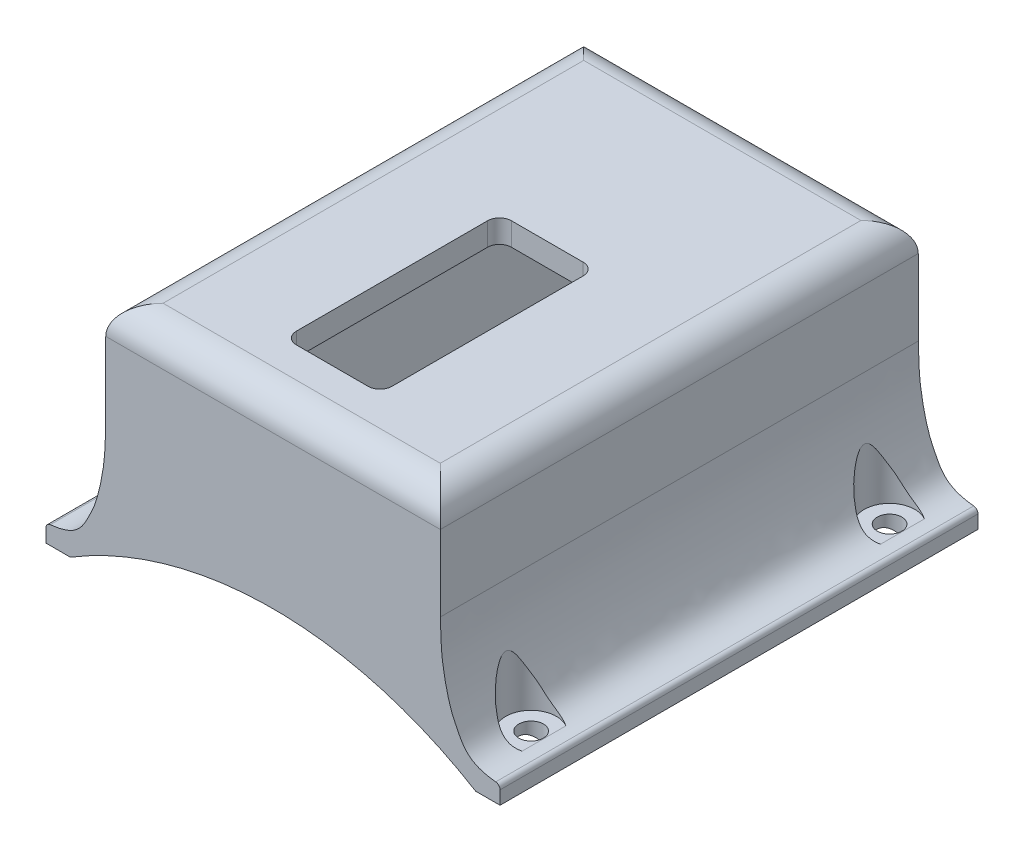
SolidWorks part; units mm, degrees
ref_plane "Front Plane" through (0, 0, 0) normal (0, 0, 1) x (1, 0, 0)
ref_plane "Top Plane" through (0, 0, 0) normal (0, 1, 0) x (1, 0, 0)
ref_plane "Right Plane" through (0, 0, 0) normal (1, 0, 0) x (0, 0, -1)
ref_axis "Axis1" through (0, 0, -60.9441) along (0, 0, 1)
sketch "Sketch1" plane through (0, 0, 0) normal (0, 1, 0) x (1, 0, 0)
  line L7 (22.225, -31.75) -> (-22.225, -31.75)
  line L8 (22.225, -31.75) -> (22.225, 31.75)
  line L9 (22.225, 31.75) -> (-22.225, 31.75)
  line L10 (-22.225, -31.75) -> (-22.225, 31.75)
  line L11 (22.225, -31.75) -> (-22.225, 31.75) construction
  line L12 (22.225, 31.75) -> (-22.225, -31.75) construction
  point P0 (0, 0)
  point P6 (0, 0)
  dimension "D1" = 44.45
  dimension "D3" = 63.5
extrude "Boss-Extrude1" add sketch "Sketch1" along normal blind 27.7622
sketch "Sketch3" plane through (0, 0, 0) normal (0, -1, 0) x (1, 0, 0)
  line L1 (19.304, -28.575) -> (-19.304, -28.575)
  line L2 (19.304, -28.575) -> (19.304, 27.94)
  line L3 (19.304, 27.94) -> (-19.304, 27.94)
  line L4 (-19.304, -28.575) -> (-19.304, 27.94)
  line L5 (19.304, -28.575) -> (-19.304, 27.94) construction
  line L6 (19.304, 27.94) -> (-19.304, -28.575) construction
  line L7 (22.225, -31.75) -> (-22.225, -31.75) construction
  point P0 (0, -0.3175)
  dimension "D1" = 38.608
  dimension "D2" = 56.515
  dimension "D3" = 3.175
extrude "Cut-Extrude2" cut sketch "Sketch3" against normal blind 24.7142
sketch "Sketch2" plane through (0, 0, -31.75) normal (0, 0, -1) x (-1, 0, 0)
  line L0 (-19.304, 0) -> (19.304, 0) construction
  line L3 (-14.2875, 1.7214) -> (-14.2875, 15.7951)
  line L5 (5.3975, 24.6851) -> (-5.3975, 24.6851)
  line L8 (-22.225, 0) -> (22.225, 0) construction
  line L11 (14.2875, 15.7951) -> (14.2875, 1.7214)
  arc A1 (5.3975, 24.6851) -> (10.4775, 19.6051) centre (5.3975, 19.6051) cw
  arc A2 (-5.3975, 24.6851) -> (-10.4775, 19.6051) centre (-5.3975, 19.6051) ccw
  arc A4 (14.2875, 1.7214) -> (-14.2875, 1.7214) centre (0, -48.0859) ccw
  circle A5 centre (0, -48.0859) radius 51.816 construction
  arc A6 (14.2875, 15.7951) -> (10.4775, 19.6051) centre (10.4775, 15.7951) ccw
  arc A7 (-10.4775, 19.6051) -> (-14.2875, 15.7951) centre (-10.4775, 15.7951) ccw
  point P3 (0, 3.7301)
  point P12 (0, 0)
  point P18 (-10.4775, 24.6851)
  point P19 (0, 0)
  point P23 (0, 0)
  point P24 (0, 0)
  point P25 (0, 0)
  point P27 (0, 0)
  point P28 (14.2875, 19.6051)
  point P31 (0, 0)
  point P32 (0, 0)
  point P33 (0, 0)
  point P34 (0, 0)
  point P35 (0, 0)
  point P36 (-14.2875, 13.7552)
  point P37 (0, 0)
  point P38 (0, 0)
  point P39 (0, 24.6851)
  dimension "D1" = 103.632
  dimension "D3" = 38.608
  dimension "D2" = 20.955
  dimension "D5" = 28.575
  dimension "D7" = 15.875
extrude "Cut-Extrude3" cut sketch "Sketch2" against normal up to surface (3.175 mm away) up to face at (0, 12.3571, -28.575)
sketch "Sketch6" plane through (0, 0, -31.75) normal (0, 0, -1) x (-1, 0, 0)
  line L1 (-22.225, 27.7622) -> (-22.225, 0) construction
  line L3 (-22.225, 0) -> (-22.225, 13.8811)
  line L6 (0, 15.2692) -> (0, -15.2692) construction
  line L9 (22.225, 0) -> (22.225, 13.8811)
  line L10 (-30.1625, -3.81) -> (30.1625, -3.81)
  line L11 (30.1625, -3.81) -> (30.1625, -1.4483)
  line L12 (-22.225, 0) -> (22.225, 0)
  line L13 (-30.1625, -1.4483) -> (-30.1625, -3.81)
  spline S0 degree 3 poles (-22.225, 13.8811) (-22.3095, 11.7348) (-22.2934, 9.3495) (-23.3442, 4.4268) (-25.2313, 0.5556) (-26.0119, -1.1813) (-30.1625, -1.4483) knots 0 0 0 0 0.208478 0.455524 0.521663 1 1 1 1
  spline S1 degree 3 poles (22.225, 13.8811) (22.3095, 11.7348) (22.2934, 9.3495) (23.3442, 4.4268) (25.2313, 0.5556) (26.0119, -1.1813) (30.1625, -1.4483) knots 0 0 0 0 0.208478 0.455524 0.521663 1 1 1 1
  point P13 (0, -3.81)
  dimension "D1" = 3.81
  dimension "D2" = 7.9375
extrude "Boss-Extrude2" add sketch "Sketch6" against normal up to surface (63.5 mm away) up to face at (0, 13.8811, 31.75)
fillet "Fillet1" radius 3.81 4 edges at (0, 27.7622, 31.75) (-22.225, 27.7622, 0) (0, 27.7622, -31.75) (22.225, 27.7622, 0)
sketch "Sketch5" plane through (0, 0, -31.75) normal (0, 0, -1) x (-1, 0, 0)
  circle A2 centre (0, -48.0859) radius 51.816
  arc A5 (14.2875, 1.7214) -> (-14.2875, 1.7214) centre (0, -48.0859) ccw construction
  dimension "D1" = 103.632
extrude "Cut-Extrude6" cut sketch "Sketch5" against normal through all
fillet "Fillet4" radius 0.635 2 edges at (-30.1625, -1.4483, 0) (30.1625, -1.4483, 0)
hole_wizard "CBORE for #4 Binding Head Machine Screw2" positions "Sketch18" profile "Sketch19" counterbore size "#4" standard "ANSI Inch" end condition through all
sketch "Sketch18" plane through (0, 27.7622, 0) normal (0, 1, 0) x (1, 0, 0)
  line L0 (-22.225, 31.75) -> (-29.5912, 31.75) construction
  line L1 (-29.5912, -31.75) -> (-22.225, -31.75) construction
  line L2 (-30.1625, -31.75) -> (-30.1625, 31.75) construction
  line L3 (0, -17.3647) -> (0, 17.3647) construction
  point P0 (-26.3525, 23.8125)
  point P2 (-26.3525, -23.8125)
  point P15 (26.3525, -23.8125)
  point P16 (26.3525, 23.8125)
  dimension "D1" = 7.9375
  dimension "D2" = 7.9375
  dimension "D3" = 3.81
sketch "Sketch19" plane through (-26.3525, 27.7622, -23.8125) normal (1, 0, 0) x (0, 0, 1)
  line L0 (0, 0) -> (0, 31.5722)
  line L1 (0, 31.5722) -> (1.6319, 31.5722)
  line L3 (1.6319, 31.5722) -> (1.6319, 28.9052)
  line L4 (1.6319, 28.9052) -> (3.3731, 28.9052)
  line L5 (3.3731, 28.9052) -> (3.3731, 0)
  line L7 (3.3731, 0) -> (0, 0)
  line L11 (0, -6.35) -> (0, 107.95) construction
  dimension "Thru Hole Dia." = 3.2639
  dimension "Thru Hole Depth" = 31.5722
  dimension "C'Bore Dia." = 6.7462
  dimension "C'Bore Depth" = 28.9052
fillet "Fillet5" radius 2.54 2 edges at (-10.4775, 19.6051, -30.1625) (10.4775, 19.6051, -30.1625)
sketch "Sketch20" plane through (0, 27.7622, 0) normal (0, 1, 0) x (1, 0, 0)
  line L0 (0, 60.9441) -> (0, -60.9441) construction
  line L1 (-6.35, -23.8837) -> (6.35, -23.8837)
  line L2 (-6.35, -23.8837) -> (-6.35, 4.6913)
  line L3 (-6.35, 4.6913) -> (6.35, 4.6913)
  line L4 (6.35, -23.8837) -> (6.35, 4.6913)
  line L5 (-6.35, -23.8837) -> (6.35, 4.6913) construction
  line L6 (-6.35, 4.6913) -> (6.35, -23.8837) construction
  line L8 (-5.3975, 31.6788) -> (5.3975, 31.6788) construction
  point P0 (0, -9.5962)
  dimension "D1" = 12.7
  dimension "D2" = 28.575
  dimension "D3" = 26.9875
extrude "Cut-Extrude7" cut sketch "Sketch20" against normal up to next
fillet "Fillet6" radius 1.5875 4 edges at (-6.35, 26.2382, 23.8837) (6.35, 26.2382, 23.8837) (-6.35, 26.2382, -4.6913) (6.35, 26.2382, -4.6913)
